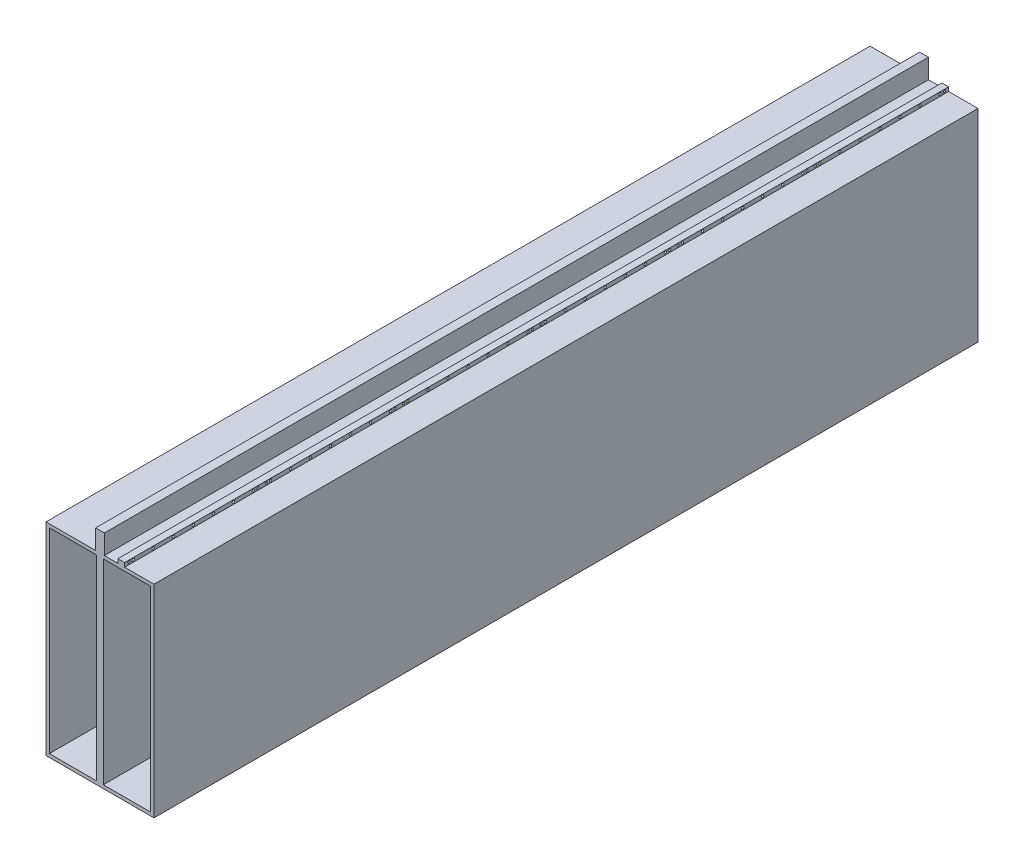
SolidWorks part; units mm, degrees
ref_plane "Plan de face" through (0, 0, 0) normal (0, 0, 1) x (1, 0, 0)
ref_plane "Plan de dessus" through (0, 0, 0) normal (0, 1, 0) x (1, 0, 0)
ref_plane "Plan de droite" through (0, 0, 0) normal (1, 0, 0) x (0, 0, -1)
sketch "Esquisse1" plane through (0, 0, 0) normal (0, 0, 1) x (1, 0, 0)
  line L0 (425, 1475) -> (425, 25)
  line L1 (0, 0) -> (800, 0)
  line L2 (0, 0) -> (0, 1500)
  line L3 (0, 1500) -> (800, 1500)
  line L4 (800, 0) -> (800, 1500)
  line L5 (25, 1475) -> (375, 1475)
  line L6 (25, 1475) -> (25, 25)
  line L7 (25, 25) -> (375, 25)
  line L8 (375, 1475) -> (375, 25)
  line L9 (425, 25) -> (775, 25)
  line L10 (775, 25) -> (775, 1475)
  line L11 (775, 1475) -> (425, 1475)
  line L12 (400, -1) -> (400, 1) construction
  point P16 (400, 0)
  dimension "D1" = 1500
  dimension "D2" = 800
  dimension "D3" = 25
  dimension "D4" = 25
  dimension "D5" = 25
  dimension "D6" = 25
  dimension "D7" = 25
  dimension "D8" = 25
  dimension "D9" = 25
  dimension "D10" = 25
extrude "Boss.-Extru.1" add sketch "Esquisse1" against normal blind 6000 and the other way blind 107.28
sketch "Esquisse2" plane through (0, 0, 107.28) normal (0, 0, 1) x (1, 0, 0)
  line L0 (400, 1500) -> (400, 1546.5728) construction
  line L1 (800, 1500) -> (0, 1500) construction
  line L2 (367.5, 1500) -> (432.5, 1500)
  line L3 (432.5, 1500) -> (432.5, 1645)
  line L4 (432.5, 1645) -> (367.5, 1645)
  line L5 (367.5, 1645) -> (367.5, 1500)
  point P7 (400, 1500)
  dimension "D1" = 65
  dimension "D2" = 145
extrude "Boss.-Extru.2" add sketch "Esquisse2" against normal up to surface (6107.28 mm away) up to face at (600, 750, -6000)
sketch "Esquisse4" plane through (0, 0, -6000) normal (0, 0, -1) x (-1, 0, 0)
  line L0 (-800, 1500) -> (-432.5, 1500) construction
  line L1 (-582.5, 1500) -> (-532.5, 1500)
  line L2 (-582.5, 1500) -> (-582.5, 1530)
  line L3 (-582.5, 1530) -> (-532.5, 1530)
  line L4 (-532.5, 1500) -> (-532.5, 1530)
  line L5 (-582.5, 1500) -> (-582.5, 1535.5) construction
  dimension "D1" = 30
  dimension "D2" = 50
extrude "Boss.-Extru.4" add sketch "Esquisse4" against normal blind 6107.28
sketch "Esquisse5" plane through (582.5, 0, 0) normal (1, 0, 0) x (0, 0, -1)
  circle A0 centre (5936.4, 1516) radius 9
  circle A1 centre (5968.6, 1516) radius 7.85
  circle A2 centre (5787.9533, 1516) radius 9
  circle A3 centre (5639.5066, 1516) radius 9
  circle A4 centre (5491.06, 1516) radius 9
  circle A5 centre (5342.6133, 1516) radius 9
  circle A6 centre (5194.1667, 1516) radius 9
  circle A7 centre (5045.72, 1516) radius 9
  circle A8 centre (5013.52, 1516) radius 7.85
extrude "Enlèv. mat.-Extru.2" cut sketch "Esquisse5" against normal blind 50
pattern_linear "Répétition linéaire1" count 6 spacing 1017.88 along (0, 0, 1) of "Enlèv. mat.-Extru.2"
